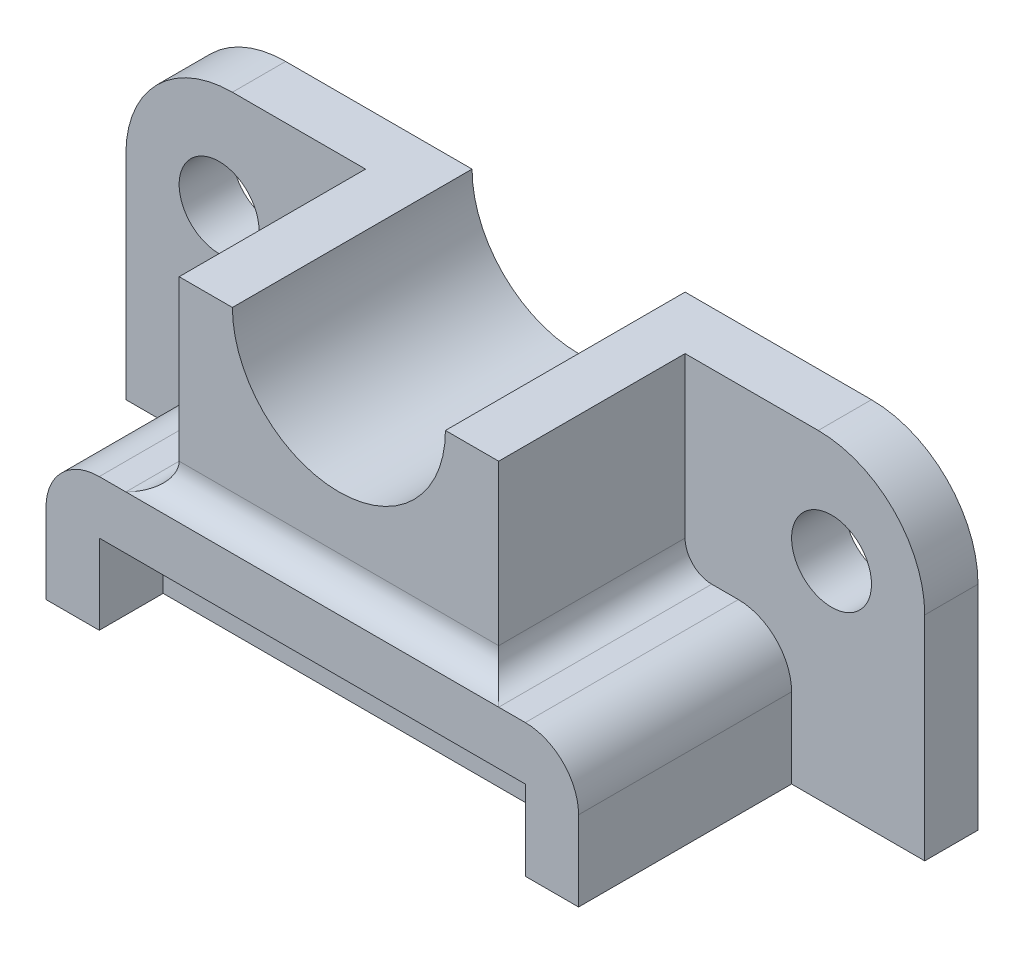
SolidWorks part; units mm, degrees
ref_plane "Plano frontal" through (0, 0, 0) normal (0, 0, 1) x (1, 0, 0)
ref_plane "Plano superior" through (0, 0, 0) normal (0, 1, 0) x (1, 0, 0)
ref_plane "Plano direito" through (0, 0, 0) normal (1, 0, 0) x (0, 0, -1)
sketch "Esboço1" plane through (0, 0, 0) normal (0, 0, 1) x (1, 0, 0)
  line L1 (75, -30) -> (-75, -30)
  line L2 (75, -30) -> (75, 30)
  line L3 (75, 30) -> (-75, 30)
  line L4 (-75, -30) -> (-75, 30)
  line L5 (75, -30) -> (-75, 30) construction
  line L6 (75, 30) -> (-75, -30) construction
  point P0 (0, 0)
  dimension "D1" = 150
  dimension "D2" = 60
extrude "Ressalto-extrusão1" add sketch "Esboço1" along normal blind 10
sketch "Esboço3" plane through (0, 0, 10) normal (0, 0, 1) x (1, 0, 0)
  line L1 (-75, -30) -> (75, -30) construction
  line L2 (-40, -30) -> (-40, -15)
  line L3 (-40, -15) -> (40, -15)
  line L4 (40, -15) -> (40, -30)
  line L6 (40, -30) -> (50, -30)
  line L7 (50, -30) -> (50, -5)
  line L8 (50, -5) -> (-50, -5)
  line L9 (-50, -5) -> (-50, -30)
  line L11 (-50, -30) -> (-40, -30)
  line L12 (40, -30) -> (50, -30)
  line L13 (-50, -30) -> (-40, -30)
  line L14 (40, -30) -> (50, -30)
  line L15 (75, 30) -> (-75, 30) construction
  point P0 (0, -15)
  point P7 (0, -5)
  line M5 (-75, -30) -> (75, -30)
  dimension "D1" = 80
  dimension "D2" = 15
  dimension "D3" = 10
  dimension "D4" = 100
  dimension "D5" = 25
  dimension "D6" = 10
  dimension "D7" = 25
  dimension "D8" = 25
  dimension "D9" = 35
extrude "Ressalto-extrusão2" add sketch "Esboço3" along normal blind 40 contours L8 L9 L2 L3 L4 L7 M5 region at (0, -12.8846, 10)
fillet "Filete1" radius 20 2 edges at (75, 30, 5) (-75, 30, 5)
fillet "Filete2" radius 10 2 edges at (-50, -5, 30) (50, -5, 30)
sketch "Esboço4" plane through (0, 0, 0) normal (0, 0, 1) x (1, 0, 0)
  line L0 (50, -30) -> (75, -30) construction
  circle A0 centre (-57.5, 10) radius 7.5
  circle A1 centre (57.5, 10) radius 7.5
  dimension "D1" = 15
  dimension "D2" = 15
  dimension "D3" = 115
  dimension "D4" = 17.5
  dimension "D5" = 17.5
  dimension "D6" = 40
extrude "Corte-extrusão2" cut sketch "Esboço4" against normal blind 10 and the other way blind 10
sketch "Esboço5" plane through (0, 0, 0) normal (0, 0, 1) x (1, 0, 0)
  line L0 (40, -5) -> (-40, -5) construction
  line L1 (-30, -5) -> (30, -5)
  line L2 (-30, -5) -> (-30, 30)
  line L3 (-30, 30) -> (30, 30)
  line L4 (30, -5) -> (30, 30)
  line L5 (55, 30) -> (-55, 30) construction
  circle A0 centre (0, 30) radius 20
  point P8 (0, 30)
  dimension "D2" = 40
  dimension "D1" = 60
extrude "Ressalto-extrusão5" add sketch "Esboço5" along normal blind 35 from surface contours A0 L3 L2 L1 L4 region at (0, 8.6525, 0) starting at face at (-50, 10, 10)
sketch "Esboço7" plane through (0, 0, 10) normal (0, 0, 1) x (1, 0, 0)
  line L0 (20, 30) -> (-20, 30) construction
  circle A0 centre (0, 30) radius 20
  dimension "D1" = 40
extrude "Corte-extrusão3" cut sketch "Esboço7" against normal blind 10
fillet "Filete4" radius 5 3 edges at (-30, -5, 27.5) (30, -5, 27.5) (0, -5, 45)
sketch "Esboço8" plane through (0, 0, 0) normal (0, 0, 1) x (1, 0, 0)
  line L1 (40, -30) -> (-40, -30)
  line L2 (40, -30) -> (40, -15)
  line L3 (40, -15) -> (-40, -15)
  line L4 (-40, -30) -> (-40, -15)
extrude "Ressalto-extrusão6" add sketch "Esboço8" along normal blind 38
